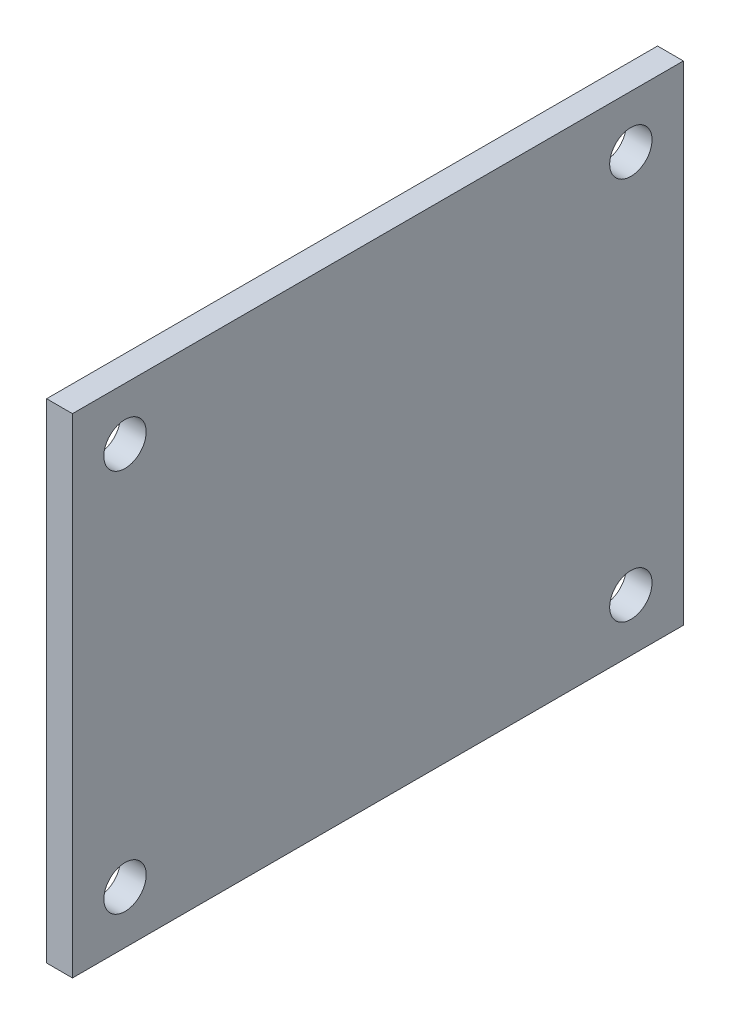
SolidWorks part; units mm, degrees
ref_plane "Front Plane" through (0, 0, 0) normal (0, 0, 1) x (1, 0, 0)
ref_plane "Top Plane" through (0, 0, 0) normal (0, 1, 0) x (1, 0, 0)
ref_plane "Right Plane" through (0, 0, 0) normal (1, 0, 0) x (0, 0, -1)
sketch "Sketch1" plane through (0, 0, 0) normal (1, 0, 0) x (0, 0, -1)
  line L1 (-37.5, -30) -> (37.5, -30)
  line L2 (-37.5, -30) -> (-37.5, 30)
  line L3 (-37.5, 30) -> (37.5, 30)
  line L4 (37.5, -30) -> (37.5, 30)
  line L5 (-37.5, -30) -> (37.5, 30) construction
  line L6 (-37.5, 30) -> (37.5, -30) construction
  point P0 (0, 0)
  dimension "D1" = 75
  dimension "D2" = 60
extrude "Boss-Extrude1" add sketch "Sketch1" along normal blind 1.5875 and the other way blind 1.5875
sketch "Sketch2" plane through (0, 0, 0) normal (1, 0, 0) x (0, 0, -1)
  line L0 (-37.5, 30) -> (-31.05, 30) construction
  line L1 (37.5, 30) -> (-37.5, 30) construction
  line L2 (-31.05, 30) -> (-31.05, 23.55) construction
  line L3 (0, 1.7463) -> (0, -1.7463) construction
  line L4 (1.7463, 0) -> (-1.7463, 0) construction
  circle A0 centre (-31.05, 23.55) radius 2.6
  circle A1 centre (31.05, 23.55) radius 2.6
  circle A2 centre (31.05, -23.55) radius 2.6
  circle A3 centre (-31.05, -23.55) radius 2.6
  dimension "D3" = 5.2
  dimension "D1" = 6.45
  dimension "D2" = 6.45
extrude "Cut-Extrude1" cut sketch "Sketch2" against normal through all both and the other way through all
